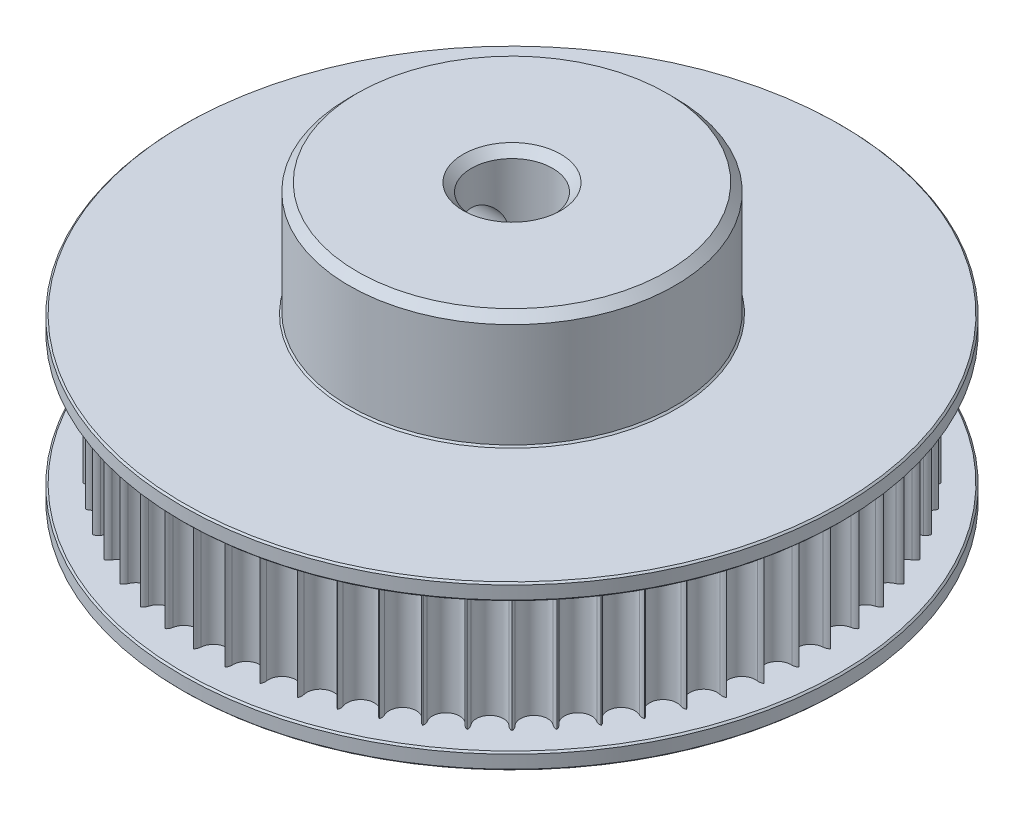
SolidWorks part; units mm, degrees
ref_plane "Front plan" through (0, 0, 0) normal (0, 0, 1) x (1, 0, 0)
ref_plane "Top plan" through (0, 0, 0) normal (0, 1, 0) x (1, 0, 0)
ref_plane "Right plan" through (0, 0, 0) normal (1, 0, 0) x (0, 0, -1)
sketch "Skica2" plane through (0, 0, 0) normal (0, 0, 1) x (1, 0, 0)
  line L0 (10, 9) -> (2.5, 9)
  line L1 (2.5, 9) -> (2.5, -9)
  line L2 (2.5, -9) -> (3.5, -9)
  line L3 (0, -9) -> (0, 9) construction
  line L4 (0, 9) -> (2.5, 9)
  line L5 (0, -9) -> (2.5, -9)
  line L6 (3.5, -9) -> (3.5, -8)
  line L7 (20.25, 1) -> (18.8, 1)
  line L8 (18.8, 1) -> (18.8, -7)
  line L9 (20.25, 1) -> (20.25, 2)
  line L12 (20.25, -8) -> (3.5, -8)
  line L13 (20.25, 2) -> (10, 2)
  line L14 (20.25, -8) -> (20.25, -7)
  line L15 (18.8, -7) -> (20.25, -7)
  line L16 (10, 2) -> (10, 9)
  point P2 (6.9432, -7.5)
  point P6 (11.875, -8)
  point P7 (0, 0)
  point P17 (7.5179, -7.5)
  dimension "D2" = 1
  dimension "D6" = 40.5
  dimension "D3" = 37.6
  dimension "D1" = 5
  dimension "D8" = 18
  dimension "D4" = 1
  dimension "D7" = 20
  dimension "D9" = 7
  dimension "D5" = 1
revolve "Revolute" add sketch "Skica2" angle 360 about L3 region at (9.6796, -0.9911, 0)
sketch "Sketch2" plane through (0, 1, 0) normal (0, -1, 0) x (1, 0, 0)
  line L0 (0, 0) -> (0, 18.3305) construction
  line L1 (0, 0) -> (6.3393, 17.699) construction
  line L3 (0, 0) -> (-2.1448, 18.6773) construction
  circle A1 centre (0, 0) radius 17.4945 construction
  circle A2 centre (0, 0) radius 18.3 construction
  arc A3 (-0.8345, 18.281) -> (0.8345, 18.281) centre (0, 18.3305) ccw
  arc A7 (-1.3701, 18.75) -> (-2.1448, 18.6773) centre (0, 0) ccw
  arc A8 (0, 20.2554) -> (2.1448, 18.6773) centre (0.5756, 18.7912) cw
  circle A9 centre (0, 0) radius 18.8 construction
  arc A10 (1.3701, 18.75) -> (2.1448, 18.6773) centre (0, 0) cw
  arc A11 (1.3701, 18.75) -> (0.8345, 18.281) centre (1.3336, 18.2513) ccw
  arc A12 (0, 20.2554) -> (-2.1448, 18.6773) centre (-0.5756, 18.7912) ccw
  arc A13 (-1.3701, 18.75) -> (-0.8345, 18.281) centre (-1.3336, 18.2513) cw
  point P0 (0.8326, 11.926)
  dimension "D2" = 1
  dimension "D4" = 0.836
  dimension "D6" = 37.6
  dimension "D3" = 1.5733
extrude "Cut-Extrude3" cut sketch "Sketch2" along normal up to surface (8 mm away) up to face at (20.25, -7, 0)
pattern_circular "CirPattern1" count 60 over 360 about axis through (0, -9, 0) along (0, -1, 0) of "Cut-Extrude3"
sketch "Sketch3" plane through (0, 0, 0) normal (1, 0, 0) x (0, 0, -1)
  line L0 (0, 9) -> (0, 0.5) construction
  line L1 (2.5, 9) -> (-2.5, 9) construction
  circle A0 centre (0, 4.75) radius 1.65
  dimension "D1" = 3.3
extrude "Cut-Extrude2" cut sketch "Sketch3" against normal up to next
chamfer "Chamfer1" distance 1 angle 45 1 edges at (3.5, -8, 0)
chamfer "Chamfer2" distance 0.5 angle 45 2 edges at (10, 9, 0) (2.5, 9, 0)
chamfer "Chamfer3" distance 0.1 angle 45 5 edges at (20.25, -8, 0) (20.25, -7, 0) (20.25, 1, 0) (20.25, 2, 0) (10, 2, 0)
equation "\"`\"=2"
equation "\"D6@Sketch2\"= \"D3@Skica2\""
